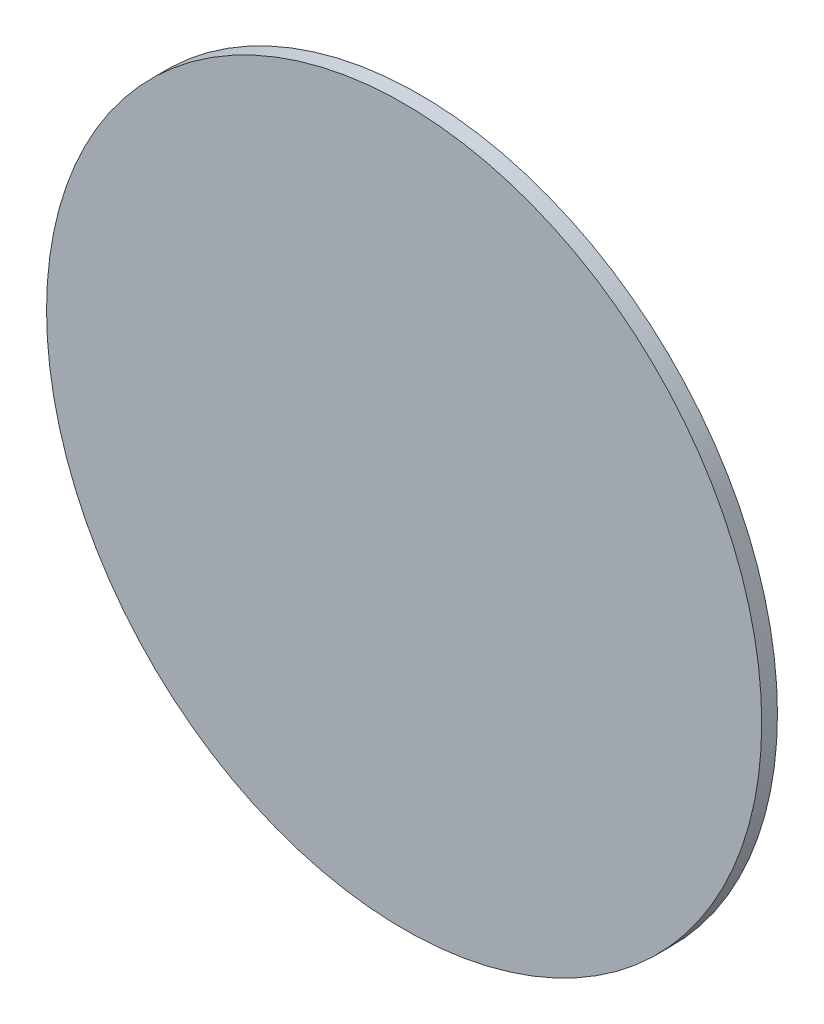
SolidWorks part; units mm, degrees
material "ﾎﾟﾘｴﾁﾚﾝﾃﾚﾌﾀﾗｰﾄ(PET)"
ref_plane "正面" through (0, 0, 0) normal (0, 0, 1) x (1, 0, 0)
ref_plane "平面" through (0, 0, 0) normal (0, 1, 0) x (1, 0, 0)
ref_plane "右側面" through (0, 0, 0) normal (1, 0, 0) x (0, 0, -1)
sketch "ｽｹｯﾁ1" plane through (0, 0, 0) normal (0, 0, 1) x (1, 0, 0)
  circle A0 centre (0, 0) radius 125
  dimension "D1" = 250
extrude "ﾎﾞｽ - 押し出し1" add sketch "ｽｹｯﾁ1" along normal blind 5.5
sketch "ｽｹｯﾁ2" plane through (0, 0, 0) normal (0, 1, 0) x (1, 0, 0)
  line L0 (0, 0) -> (0, -50)
  point P3 (0, -46.271)
  dimension "D1" = 50
